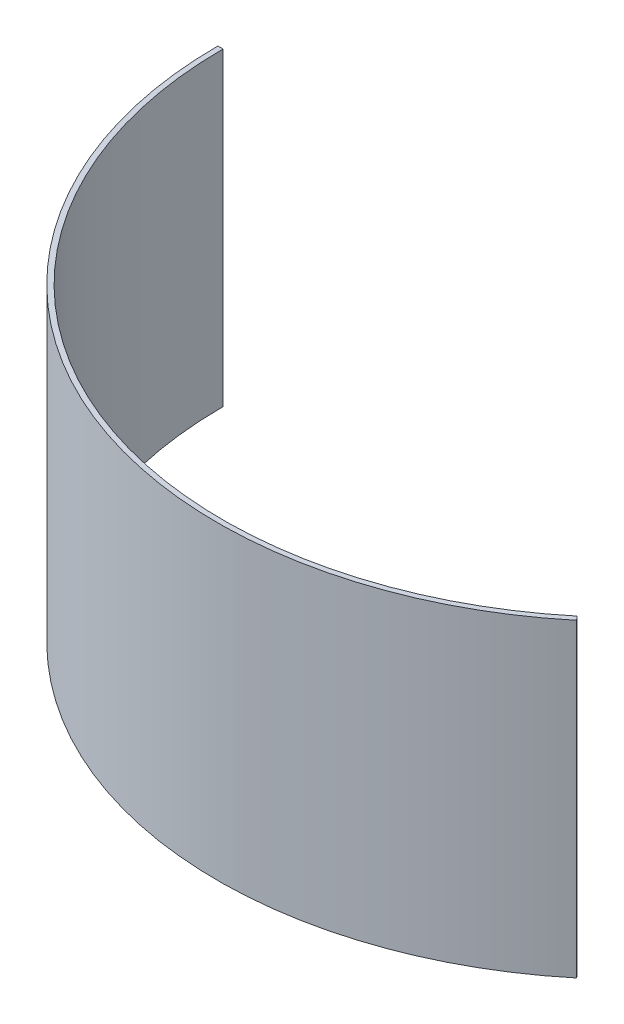
SolidWorks part; units mm, degrees
ref_plane "Front Plane" through (0, 0, 0) normal (0, 0, 1) x (1, 0, 0)
ref_plane "Top Plane" through (0, 0, 0) normal (0, 1, 0) x (1, 0, 0)
ref_plane "Right Plane" through (0, 0, 0) normal (1, 0, 0) x (0, 0, -1)
sketch "Sketch1" plane through (0, 0, 0) normal (0, 0, 1) x (1, 0, 0)
  line L0 (0, 0) -> (0, 152.4)
  line L1 (0, 152.4) -> (2.54, 152.4)
  line L2 (2.54, 152.4) -> (2.54, 0)
  line L3 (2.54, 0) -> (0, 0)
  line L4 (203.2, 0) -> (203.2, 152.4)
  dimension "D1" = 2.54
  dimension "D2" = 152.4
  dimension "D3" = 203.2
revolve "Revolve1" add sketch "Sketch1" angle 129.66 about L4 region at (1.27, 76.2, 0)
